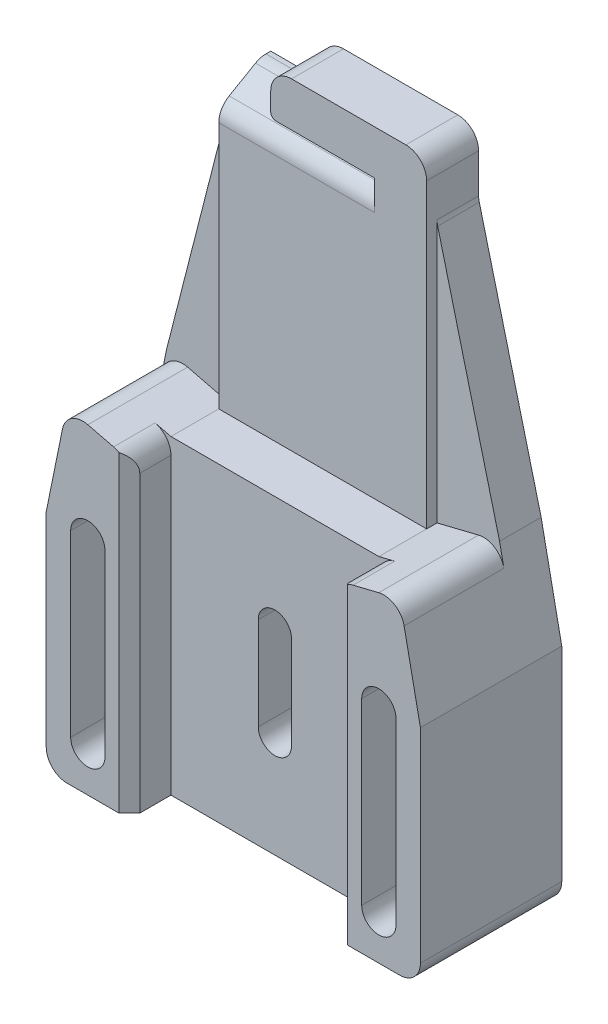
SolidWorks part; units mm, degrees
ref_plane "Front Plane" through (0, 0, 0) normal (0, 0, 1) x (1, 0, 0)
ref_plane "Top Plane" through (0, 0, 0) normal (0, 1, 0) x (1, 0, 0)
ref_plane "Right Plane" through (0, 0, 0) normal (1, 0, 0) x (0, 0, -1)
sketch "Sketch1" plane through (0, 0, 0) normal (0, 0, 1) x (1, 0, 0)
  line L0 (0, 0) -> (10, 0) construction
  line L1 (0, 0) -> (0, 10) construction
  line L2 (-143.3708, 41.2466) -> (77.8135, -51.9066) construction
  line L3 (74.9025, -58.8186) -> (-146.2818, 34.3346) construction
  line L4 (71.9914, -65.7306) -> (-149.1928, 27.4226) construction
  line L5 (-143.3708, 41.2466) -> (77.8135, -51.9066) construction
  line L6 (74.9025, -58.8186) -> (-146.2818, 34.3346) construction
  line L7 (71.9914, -65.7306) -> (-149.1928, 27.4226) construction
  line L8 (5, 15) -> (-5, 15) construction
  line L9 (-5, 16) -> (5, 16) construction
  line L10 (5, 16) -> (5, 15) construction
  line L11 (-5, 15) -> (-5, 16) construction
  line L12 (12.35, -30.4565) -> (12.35, -35.8818) construction
  line L13 (15.65, -35.8818) -> (15.65, -30.4565) construction
  line L14 (1.65, -24.5603) -> (1.65, -29.9856) construction
  line L15 (-1.65, -29.9856) -> (-1.65, -24.5603) construction
  line L16 (-12.35, -24.0894) -> (-12.35, -18.6641) construction
  line L17 (-15.65, -18.6641) -> (-15.65, -24.0894) construction
  line L18 (5, 15) -> (-5, 15) construction
  line L19 (-5, 16) -> (5, 16) construction
  line L20 (5, 16) -> (5, 15) construction
  line L21 (-5, 15) -> (-5, 16) construction
  line L22 (12.35, -30.4565) -> (12.35, -35.8818)
  line L23 (15.65, -35.8818) -> (15.65, -30.4565)
  line L24 (1.65, -24.5603) -> (1.65, -29.9856) construction
  line L25 (-1.65, -29.9856) -> (-1.65, -24.5603) construction
  line L26 (-12.35, -24.0894) -> (-12.35, -18.6641)
  line L27 (-15.65, -18.6641) -> (-15.65, -24.0894)
  line L28 (0, 0) -> (0, -35.411) construction
  line L29 (-15.65, -35.8818) -> (-15.65, -30.4565)
  line L30 (-12.35, -30.4565) -> (-12.35, -35.8818)
  line L31 (15.65, -18.6641) -> (15.65, -24.0894)
  line L32 (12.35, -24.0894) -> (12.35, -18.6641)
  line L33 (143.3708, 41.2466) -> (-77.8135, -51.9066) construction
  line L34 (-74.9025, -58.8186) -> (146.2818, 34.3346) construction
  line L35 (-71.9914, -65.7306) -> (149.1928, 27.4226) construction
  circle A0 centre (0, 0) radius 10 construction
  circle A1 centre (0, 0) radius 10 construction
  circle A2 centre (0, 72.5) radius 82.5 construction
  circle A3 centre (0, 72.5) radius 82.5 construction
  arc A4 (15.65, -30.4565) -> (12.35, -30.4565) centre (14, -30.4565) ccw construction
  arc A5 (12.35, -35.8818) -> (15.65, -35.8818) centre (14, -35.8818) ccw construction
  arc A6 (-1.65, -29.9856) -> (1.65, -29.9856) centre (0, -29.9856) ccw construction
  arc A7 (1.65, -24.5603) -> (-1.65, -24.5603) centre (0, -24.5603) ccw construction
  arc A8 (-15.65, -24.0894) -> (-12.35, -24.0894) centre (-14, -24.0894) ccw construction
  arc A9 (-12.35, -18.6641) -> (-15.65, -18.6641) centre (-14, -18.6641) ccw construction
  circle A10 centre (-14, -18.6641) radius 4 construction
  circle A11 centre (0, -24.5603) radius 4 construction
  circle A12 centre (14, -30.4565) radius 4 construction
  arc A13 (15.65, -30.4565) -> (12.35, -30.4565) centre (14, -30.4565) ccw
  arc A14 (12.35, -35.8818) -> (15.65, -35.8818) centre (14, -35.8818) ccw
  arc A15 (-1.65, -29.9856) -> (1.65, -29.9856) centre (0, -29.9856) ccw construction
  arc A16 (1.65, -24.5603) -> (-1.65, -24.5603) centre (0, -24.5603) ccw construction
  arc A17 (-15.65, -24.0894) -> (-12.35, -24.0894) centre (-14, -24.0894) ccw
  arc A18 (-12.35, -18.6641) -> (-15.65, -18.6641) centre (-14, -18.6641) ccw
  circle A19 centre (-14, -18.6641) radius 4 construction
  circle A20 centre (0, -24.5603) radius 4 construction
  circle A21 centre (14, -30.4565) radius 4 construction
  circle A22 centre (-14, -30.4565) radius 4 construction
  arc A23 (-12.35, -35.8818) -> (-15.65, -35.8818) centre (-14, -35.8818) cw
  arc A24 (-15.65, -30.4565) -> (-12.35, -30.4565) centre (-14, -30.4565) cw
  arc A25 (12.35, -18.6641) -> (15.65, -18.6641) centre (14, -18.6641) cw
  arc A26 (15.65, -24.0894) -> (12.35, -24.0894) centre (14, -24.0894) cw
  circle A27 centre (14, -18.6641) radius 4 construction
  dimension "D1" = 20
sketch "Sketch2" plane through (0, 0, 0) normal (0, 0, 1) x (1, 0, 0)
  line L0 (10, 21) -> (23.5124, -45.3134) construction
  line L1 (-18, -39.8818) -> (-18, -18.2607)
  line L2 (-19.7958, -27.0738) -> (-10, 21) construction
  line L3 (-10, 21) -> (10, 21) construction
  line L4 (10, 21) -> (22.4056, -39.8818) construction
  line L5 (22.4056, -39.8818) -> (-22.4056, -39.8818) construction
  line L6 (-22.4056, -39.8818) -> (-10, 21) construction
  line L7 (-10, 21) -> (10, 21)
  line L8 (0, -39.8818) -> (0, 21) construction
  line L9 (10, 21) -> (10, -10) construction
  line L10 (10, -10) -> (-10, -10) construction
  line L11 (-10, -10) -> (-10, 21) construction
  line L12 (10, -10) -> (16.0152, -8.52) construction
  line L13 (-10, -10) -> (-16.0152, -8.52) construction
  line L14 (-12.35, -24.0894) -> (-12.35, -18.6641) construction
  line L15 (-15.65, -18.6641) -> (-15.65, -24.0894) construction
  line L18 (12.35, -30.4565) -> (12.35, -35.8818) construction
  line L19 (15.65, -35.8818) -> (15.65, -30.4565) construction
  line L20 (-12.35, -24.0894) -> (-12.35, -18.6641) construction
  line L21 (-15.65, -18.6641) -> (-15.65, -24.0894) construction
  line L22 (-1.6, -29.9856) -> (-1.6, -21.0509)
  line L23 (1.6, -21.0509) -> (1.6, -29.9856)
  line L24 (12.35, -30.4565) -> (12.35, -35.8818) construction
  line L25 (15.65, -35.8818) -> (15.65, -30.4565) construction
  line L26 (-19.7958, -27.0738) -> (23.5124, -45.3134) construction
  line L27 (19.7958, -27.0738) -> (-23.5124, -45.3134) construction
  line L28 (-71.9914, -65.7306) -> (149.1928, 27.4226) construction
  line L29 (71.9914, -65.7306) -> (-149.1928, 27.4226) construction
  line L30 (-12.35, -30.4565) -> (-12.35, -35.8818) construction
  line L31 (-15.65, -35.8818) -> (-15.65, -30.4565) construction
  line L32 (-12.35, -30.4565) -> (-12.35, -35.8818) construction
  line L33 (-15.65, -35.8818) -> (-15.65, -30.4565) construction
  line L34 (12.35, -24.0894) -> (12.35, -18.6641) construction
  line L35 (15.65, -18.6641) -> (15.65, -24.0894) construction
  line L36 (12.35, -24.0894) -> (12.35, -18.6641) construction
  line L37 (15.65, -18.6641) -> (15.65, -24.0894) construction
  line L38 (18, -39.8818) -> (18, -18.2607)
  line L39 (-18, -18.2607) -> (-10, 21)
  line L40 (10, 21) -> (18, -18.2607)
  line L41 (18, -39.8818) -> (-18, -39.8818)
  line L42 (22.3031, -39.3788) -> (-18.7777, -22.0773) construction
  line L43 (15.65, -35.8818) -> (15.65, -18.6641)
  line L44 (12.35, -18.6641) -> (12.35, -35.8818)
  line L45 (-12.35, -35.8818) -> (-12.35, -18.6641)
  line L46 (-15.65, -18.6641) -> (-15.65, -35.8818)
  circle A0 centre (0, 0) radius 10 construction
  circle A1 centre (0, 0) radius 10 construction
  circle A2 centre (0, 72.5) radius 82.5 construction
  arc A3 (-15.65, -24.0894) -> (-12.35, -24.0894) centre (-14, -24.0894) ccw construction
  arc A4 (-12.35, -18.6641) -> (-15.65, -18.6641) centre (-14, -18.6641) ccw construction
  circle A5 centre (0, 72.5) radius 91.9509 construction
  arc A7 (12.35, -35.8818) -> (15.65, -35.8818) centre (14, -35.8818) ccw construction
  arc A8 (15.65, -30.4565) -> (12.35, -30.4565) centre (14, -30.4565) ccw construction
  arc A9 (-15.65, -24.0894) -> (-12.35, -24.0894) centre (-14, -24.0894) ccw construction
  arc A10 (-12.35, -18.6641) -> (-15.65, -18.6641) centre (-14, -18.6641) ccw
  arc A11 (1.6, -21.0509) -> (-1.6, -21.0509) centre (0, -21.0509) ccw
  arc A12 (-1.6, -29.9856) -> (1.6, -29.9856) centre (0, -29.9856) ccw
  arc A13 (12.35, -35.8818) -> (15.65, -35.8818) centre (14, -35.8818) ccw
  arc A14 (15.65, -30.4565) -> (12.35, -30.4565) centre (14, -30.4565) ccw construction
  arc A15 (-12.35, -30.4565) -> (-15.65, -30.4565) centre (-14, -30.4565) ccw construction
  arc A16 (-15.65, -35.8818) -> (-12.35, -35.8818) centre (-14, -35.8818) ccw construction
  arc A17 (-12.35, -30.4565) -> (-15.65, -30.4565) centre (-14, -30.4565) ccw construction
  arc A18 (-15.65, -35.8818) -> (-12.35, -35.8818) centre (-14, -35.8818) ccw
  arc A19 (15.65, -18.6641) -> (12.35, -18.6641) centre (14, -18.6641) ccw construction
  arc A20 (12.35, -24.0894) -> (15.65, -24.0894) centre (14, -24.0894) ccw construction
  arc A21 (15.65, -18.6641) -> (12.35, -18.6641) centre (14, -18.6641) ccw
  arc A22 (12.35, -24.0894) -> (15.65, -24.0894) centre (14, -24.0894) ccw construction
  circle A23 centre (-14, -18.6641) radius 4 construction
  circle A24 centre (-14, -18.6641) radius 4 construction
  circle A25 centre (-14, -35.8818) radius 4 construction
  circle A26 centre (0, 72.5) radius 91.9509 construction
  dimension "D1" = 1.6
sketch "Sketch3" plane through (0, 0, 0) normal (1, 0, 0) x (0, 0, -1)
  line L0 (0, 21) -> (0, -39.8818) construction
  line L1 (0, -39.8818) -> (-13.6002, -39.8818) construction
  line L2 (-13.6002, -39.8818) -> (-13.6002, 21) construction
  line L3 (-13.6002, 21) -> (0, 21) construction
  line L4 (-5, 21) -> (-5, -10)
  line L5 (-5, -10) -> (-9.6002, -10)
  line L6 (-9.6002, -10) -> (-9.6002, -39.8818)
  line L7 (-9.6002, -39.8818) -> (0, -39.8818)
  line L8 (0, -10) -> (-13.6002, -10) construction
  line L11 (-10.7004, -10) -> (-10.7004, 21) construction
  line L12 (-6.6002, -10) -> (-6.6002, 21) construction
  line L13 (-9.1002, -10) -> (-9.1002, 21) construction
  line L14 (-10.7004, 5.5) -> (-9.1002, 5.5) construction
  line L15 (-6.6002, 5.5) -> (-5, 5.5) construction
  line L16 (-7.1002, 21) -> (-7.1002, -10) construction
  line L17 (-5, 21) -> (0, 21)
  line L18 (0, 21) -> (0, -39.8818)
  dimension "D1" = 5
  dimension "D2" = 1.6002
  dimension "D3" = 0.5
  dimension "D4" = 2
  dimension "D5" = 0.5
  dimension "D6" = 4
extrude "Boss-Extrude1" add sketch "Sketch2" along normal up to vertex (13.6002 mm away) up to point (0, 21, 13.6002)
sketch "Sketch4" plane through (0, 0, 13.6002) normal (0, 0, 1) x (1, 0, 0)
  line L0 (-22.4056, -39.8818) -> (-10, 21) construction
  line L1 (-10, 21) -> (10, 21) construction
  line L2 (10, 21) -> (22.4056, -39.8818) construction
  line L3 (-16.0152, -8.52) -> (-10, 21)
  line L4 (-10, 21) -> (10, 21)
  line L5 (10, 21) -> (16.0152, -8.52)
  line L6 (10, -10) -> (-10, -10) construction
  line L7 (10, -10) -> (-10, -10)
  line L8 (10, -10) -> (16.0152, -8.52) construction
  line L9 (10, -10) -> (16.0152, -8.52)
  line L10 (-10, -10) -> (-16.0152, -8.52) construction
  line L11 (-10, -10) -> (-16.0152, -8.52)
extrude "Cut-Extrude1" cut sketch "Sketch4" against normal up to vertex (8.6002 mm away) up to point (0, 21, 5)
sketch "Sketch5" plane through (0, 0, 5) normal (0, 0, 1) x (1, 0, 0)
  line L0 (-10, -10) -> (-16.0152, -8.52)
  line L1 (-16.0152, -8.52) -> (-10, 21)
  line L2 (-10, 21) -> (-10, -10)
  line L3 (16.0152, -8.52) -> (10, -10)
  line L4 (10, -10) -> (10, 21)
  line L5 (10, 21) -> (16.0152, -8.52)
  line L6 (10, 21) -> (22.4056, -39.8818) construction
  line L7 (10, -10) -> (16.0152, -8.52) construction
  line L8 (-10, -10) -> (-16.0152, -8.52) construction
  line L9 (-10, -10) -> (-10, 21) construction
  line L10 (-22.4056, -39.8818) -> (-10, 21) construction
  line L11 (10, 21) -> (10, -10) construction
extrude "Cut-Extrude2" cut sketch "Sketch5" against normal blind 1
sketch "Sketch6" plane through (0, 0, 5) normal (0, 0, 1) x (1, 0, 0)
  line L0 (-16.0152, -8.52) -> (-10, 21) construction
  line L1 (10, 21) -> (16.0152, -8.52) construction
  line L2 (-16.0152, -8.52) -> (-10, 21)
  line L3 (10, 21) -> (16.0152, -8.52)
  line L4 (10, -10) -> (10, 21) construction
  line L5 (-10, 21) -> (-10, -10) construction
  line L6 (10, 15) -> (10, 21)
  line L7 (-10, 21) -> (-10, 15)
  line L8 (10, 15) -> (-10, 15) construction
  line L9 (5, 15) -> (-5, 15) construction
  line L10 (16.0152, -8.52) -> (10, 15)
  line L11 (-10, 15) -> (-16.0152, -8.52)
extrude "Cut-Extrude3" cut sketch "Sketch6" against normal through all
sketch "Sketch7" plane through (0, 0, 13.6002) normal (0, 0, 1) x (1, 0, 0)
  line L0 (22.4056, -39.8818) -> (-22.4056, -39.8818) construction
  line L1 (10, -39.8818) -> (-10, -39.8818)
  line L2 (-10, 21) -> (10, 21) construction
  line L3 (-10, 21) -> (10, 21)
  line L4 (10, 21) -> (10, -39.8818)
  line L5 (-10, 21) -> (-10, -39.8818)
  line L6 (10, 21) -> (10, -10) construction
  line L7 (-10, -10) -> (-10, 21) construction
extrude "Cut-Extrude4" cut sketch "Sketch7" against normal up to vertex (4 mm away) up to point (0, -10, 9.6002)
sketch "Sketch8" plane through (0, 0, 0) normal (1, 0, 0) x (0, 0, -1)
  line L0 (0, 15) -> (-5, 15) construction
  line L1 (0, 21) -> (0, -39.8818) construction
  line L2 (0, 16) -> (-5, 16) construction
  line L3 (-5, 21) -> (-5, -10) construction
  line L4 (-5, 21) -> (0, 21) construction
  line L5 (-5, 21) -> (-5, -10) construction
  line L6 (0, 21) -> (0, -39.8818) construction
  line L7 (-5, 21) -> (0, 21) construction
  line L8 (-5, 15) -> (-1, 17.3094)
  line L9 (-1, 17.3094) -> (0, 17.3094)
  line L10 (-5, 16.1547) -> (0, 19.0415) construction
  line L11 (-4, 16.7321) -> (-5, 16.7321)
  line L12 (0, 19.0415) -> (0, 17.3094)
  line L13 (-4, 16.7321) -> (0, 19.0415)
  line L14 (-5, 15) -> (-5, 16.7321)
  dimension "D1" = 1
  dimension "D2" = 1
  dimension "D3" = 30
extrude "Cut-Extrude5" cut sketch "Sketch8" along normal up to vertex (5 mm away) and the other way through all up to point (5, 15, 0)
sketch "Sketch9" plane through (-10, 0, 0) normal (-1, 0, 0) x (0, 0, 1)
  line L4 (0, 19.0415) -> (4, 16.7321)
  line L5 (5, 16.7321) -> (5, 21)
  line L6 (5, 21) -> (0, 21)
  line L7 (0, 21) -> (0, 19.0415)
  line L8 (0, 19.0415) -> (4, 16.7321)
  line L9 (5, 16.7321) -> (5, 21)
  line L10 (5, 21) -> (0, 21)
  line L11 (0, 21) -> (0, 19.0415)
  line L13 (4, 16.7321) -> (5, 16.7321)
  line L14 (4, 16.7321) -> (5, 16.7321)
  dimension "D1" = 0
extrude "Cut-Extrude6" cut sketch "Sketch9" against normal up to vertex (5 mm away) up to point (-5, 16, 0)
chamfer "Chamfer1" distance 1 angle 45 2 edges at (-10, -24.9409, 13.6002) (10, -24.9409, 13.6002)
fillet "Fillet1" radius 2 8 edges at (10, 15, 2) (-10, 15, 2) (-5, 21, 2.5) (10, 21, 2.5) (-10, -10, 11.1002) (10, -10, 11.1002) (18, -39.8818, 6.8001) (-18, -39.8818, 6.8001)
fillet "Fillet2" radius 2 3 edges at (-2.5, 15, 5) (0, 16.7321, 4) (-2.5, 17.3094, 1)
fillet "Fillet3" radius 0.5 4 edges at (-4.9999, 19.0207, 0.0359) (-5, 16.7321, 4.7679) (-5, 16.8002, 4.0183) (-5, 18, 1.8038)
sketch "Sketch10" plane through (0, 0, 13.6002) normal (0, 0, 1) x (1, 0, 0)
  line L1 (-16.0152, -8.52) -> (-11.5222, -9.6255) construction
  line L2 (-16.0152, -8.52) -> (-16.4309, -10.5602)
  line L3 (-16.0152, -8.52) -> (-13.9933, -9.0175)
  line L5 (11.5222, -9.6255) -> (16.0152, -8.52) construction
  line L6 (16.4309, -10.5602) -> (16.0152, -8.52)
  line L7 (13.9933, -9.0175) -> (16.0152, -8.52)
  line L8 (-22.4056, -39.8818) -> (-10, 21) construction
  line L9 (10, 21) -> (22.4056, -39.8818) construction
  line L10 (11.5222, -9.6255) -> (16.0152, -8.52) construction
  arc A0 (16.4309, -10.5602) -> (13.9933, -9.0175) centre (14.4712, -10.9596) ccw
  arc A1 (-13.9933, -9.0175) -> (-16.4309, -10.5602) centre (-14.4712, -10.9596) ccw
  dimension "D1" = 2
extrude "Cut-Extrude7" cut sketch "Sketch10" against normal up to surface (9.6002 mm away) up to face at (11.5155, 2.8715, 4)
